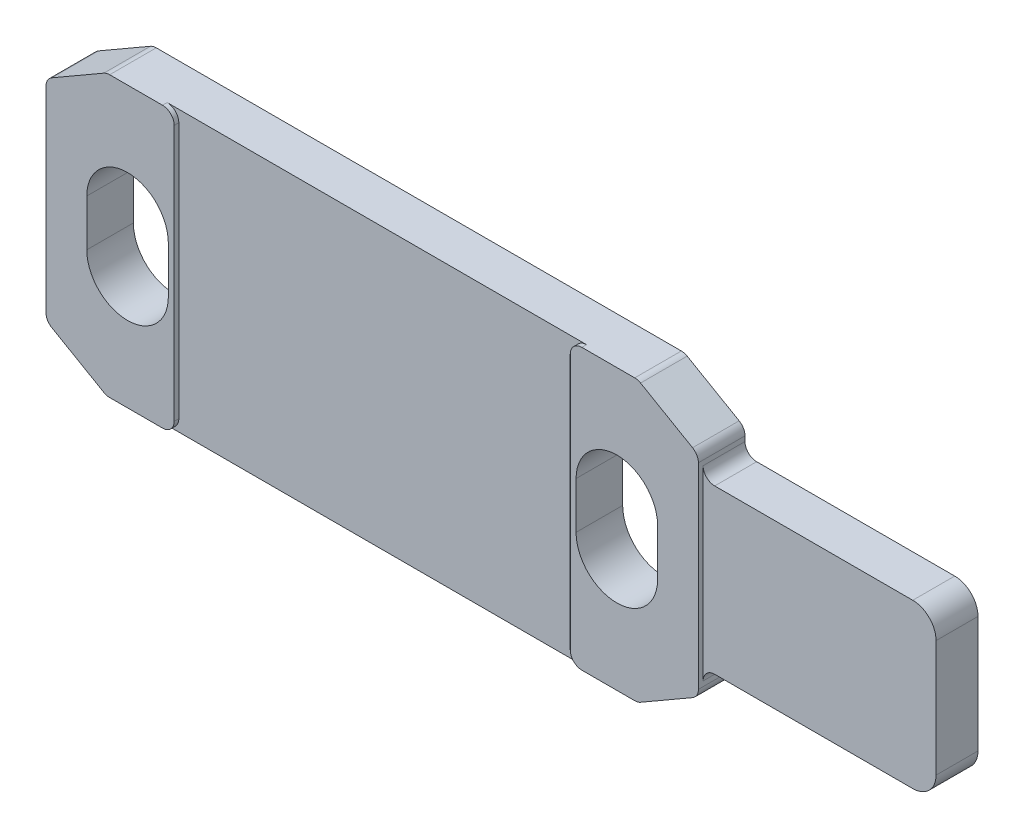
SolidWorks part; units mm, degrees
material "PET"
ref_plane "Alzado" through (0, 0, 0) normal (0, 0, 1) x (1, 0, 0)
ref_plane "Planta" through (0, 0, 0) normal (0, 1, 0) x (1, 0, 0)
ref_plane "Vista lateral" through (0, 0, 0) normal (1, 0, 0) x (0, 0, -1)
sketch "Croquis1" plane through (0, 0, 0) normal (0, 0, 1) x (1, 0, 0)
  line L0 (24.5, 0) -> (3.5, 0) construction
  line L1 (0, 6) -> (28, 6)
  line L2 (0, 6) -> (0, -6)
  line L3 (0, -6) -> (28, -6)
  line L4 (38, 3.5) -> (38, -3.5)
  line L5 (28, -6) -> (28, -3.5)
  line L6 (28, -3.5) -> (38, -3.5)
  line L7 (28, 6) -> (28, 3.5)
  line L8 (28, 3.5) -> (38, 3.5)
  line L9 (3.5, 0) -> (0, 0) construction
  line L10 (3.5, 1) -> (3.5, -1) construction
  line L11 (5.25, 1) -> (5.25, -1)
  line L12 (1.75, 1) -> (1.75, -1)
  line L13 (28, 6) -> (38, 6)
  line L14 (38, 6) -> (38, 3.5)
  line L15 (28, -6) -> (38, -6)
  line L16 (38, -6) -> (38, -3.5)
  line L17 (24.5, -1) -> (24.5, 1) construction
  line L18 (22.75, -1) -> (22.75, 1)
  line L19 (26.25, -1) -> (26.25, 1)
  line L20 (28, 3.5) -> (28, -3.5) construction
  line L21 (24.5, 0) -> (28, 0) construction
  circle A0 centre (3.5, 0) radius 1.75 construction
  circle A1 centre (24.5, 0) radius 1.75 construction
  arc A2 (5.25, 1) -> (1.75, 1) centre (3.5, 1) ccw
  arc A3 (1.75, -1) -> (5.25, -1) centre (3.5, -1) ccw
  arc A4 (22.75, -1) -> (26.25, -1) centre (24.5, -1) ccw
  arc A5 (26.25, 1) -> (22.75, 1) centre (24.5, 1) ccw
  point P2 (38, 0)
  point P5 (0, 0)
  point P19 (3.5, 0)
  point P27 (24.5, 0)
  dimension "D1" = 3.5
  dimension "D2" = 12
  dimension "D3" = 13.5
  dimension "D5" = 21
  dimension "D4" = 7
  dimension "D6" = 10
  dimension "D8" = 2
sketch "Croquis4" plane through (0, 0, 0) normal (0, 1, 0) x (1, 0, 0)
  line L0 (0, 0) -> (38, 0)
  line L1 (38, 0) -> (38, 2)
  line L2 (38, 2) -> (0, 2)
  line L3 (0, 2) -> (0, 0)
  point P5 (38, 0)
  dimension "D2" = 2
extrude "Saliente-Extruir1" add sketch "Croquis4" along normal up to vertex (6 mm away) and the other way up to vertex (6 mm away) up to point (0, 6, 0) other way up to point (0, -6, 0)
extrude "Cortar-Extruir2" cut sketch "Croquis1" against normal blind 10 contours L14 L13 L7 L8 | L15 L16 L6 L5 | A1 | A0 | L12 A3 L11 A2 | L19 A5 L18 A4
sketch "Croquis5" plane through (0, 0, 0) normal (0, 0, 1) x (1, 0, 0)
  line L0 (0, 6) -> (28, 6) construction
  line L1 (5.5, 6) -> (22.5, 6)
  line L2 (5.5, 6) -> (5.5, -6)
  line L3 (5.5, -6) -> (22.5, -6)
  line L4 (22.5, 6) -> (22.5, -6)
  line L5 (0, -6) -> (28, -6) construction
  line L6 (28, 6) -> (28, 3.5) construction
  line L7 (28, 6) -> (38, 6)
  line L8 (28, 6) -> (28, -6)
  line L9 (28, -6) -> (38, -6)
  line L10 (38, 6) -> (38, -6)
  line L12 (38, 3.5) -> (38, -3.5) construction
  dimension "D1" = 17
  dimension "D2" = 2
extrude "Cortar-Extruir3" cut sketch "Croquis5" against normal blind 0.2
fillet "Redondeo1" radius 0.5 2 edges at (28, 3.5, -1.1) (28, -3.5, -1.1)
fillet "Redondeo2" radius 0.5 4 edges at (5.5, -6, -0.1) (22.5, -6, -0.1) (22.5, 6, -0.1) (5.5, 6, -0.1)
fillet "Redondeo3" [suppressed] radius 2
fillet "Redondeo4" radius 1 2 edges at (38, -3.5, -1.1) (38, 3.5, -1.1)
chamfer "Chaflán1" distance 1.5 angle 60 4 edges at (0, 6, -1) (0, -6, -1) (28, 6, -1) (28, -6, -1)
fillet "Redondeo5" radius 0.5 8 edges at (28, -4.5, -1) (25.4019, -6, -1) (2.5981, -6, -1) (0, -4.5, -1) (0, 4.5, -1) (2.5981, 6, -1) (25.4019, 6, -1) (28, 4.5, -1)
